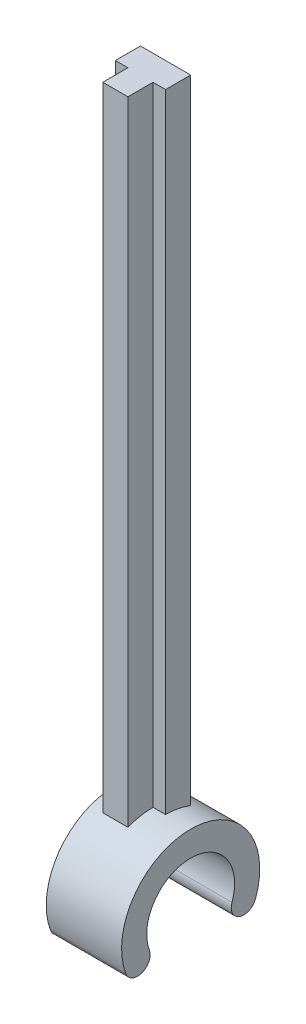
SolidWorks part; units mm, degrees
ref_plane "Front" through (0, 0, 0) normal (0, 0, 1) x (1, 0, 0)
ref_plane "Top" through (0, 0, 0) normal (0, 1, 0) x (1, 0, 0)
ref_plane "Right" through (0, 0, 0) normal (1, 0, 0) x (0, 0, -1)
sketch "Sketch1" plane through (0, 0, 0) normal (1, 0, 0) x (0, 0, -1)
  line L0 (0, 0) -> (-5.5, 0)
  line L1 (0, 0) -> (-5.1683, -1.8811)
  line L2 (0, 50) -> (0, -50) construction
  line L3 (0, 0) -> (5.1683, -1.8811)
  line L4 (-5.1683, -1.8811) -> (-4.2286, -1.5391)
  circle A0 centre (0, 0) radius 3.5
  circle A1 centre (0, 0) radius 5.5
  arc A2 (-5.1683, -1.8811) -> (-3.2889, -1.1971) centre (-4.2286, -1.5391) ccw
  arc A3 (5.1683, -1.8811) -> (3.2889, -1.1971) centre (4.2286, -1.5391) cw
  dimension "D1" = 20
  dimension "D3" = 11
  dimension "D4" = 7
  dimension "D2" = 1
extrude "Boss-Extrude1" add sketch "Sketch1" against normal blind 2 and the other way blind 4 contours L3 A1 L0 A0 | A3 L3 | L0 A1 L1 A0 | L1 A2 region at (0, -0.7903, 4.4817) region at (0, 0.1325, 4.5) region at (0, -1.9379, 4.0835) region at (0, -1.9379, -4.0835)
sketch "Sketch2" plane through (0, 0, 0) normal (1, 0, 0) x (0, 0, -1)
  line L0 (0, 0) -> (0, 5.5)
  line L1 (0, 5.5) -> (0, 3.5)
  line L2 (0, 3.5) -> (-2, 3.5)
  line L3 (0, 55.5) -> (0, 3.5)
  line L4 (-2, 3.5) -> (2, 3.5)
  line L5 (-2, 3.5) -> (-2, 55.5)
  line L6 (-2, 55.5) -> (2, 55.5)
  line L7 (2, 3.5) -> (2, 55.5)
  arc A0 (5.1683, -1.8811) -> (-5.1683, -1.8811) centre (0, 0) ccw construction
  dimension "D1" = 2
  dimension "D2" = 2
  dimension "D3" = 4
  dimension "D4" = 52
extrude "Boss-Extrude2" add sketch "Sketch2" along normal blind 2 and the other way blind 2 contours L4 L7 L6 L3 L0 region at (0, 29.5, -1)
sketch "Sketch3" plane through (0, 0, 0) normal (1, 0, 0) x (0, 0, -1)
  line L5 (0, 55.5) -> (-2, 55.5)
  line L6 (0, 55.5) -> (0, 3.5)
  line L7 (0, 3.5) -> (-2, 3.5)
  line L8 (-2, 55.5) -> (-2, 3.5)
  dimension "D1" = 52
  dimension "D2" = 2
extrude "Boss-Extrude3" add sketch "Sketch3" along normal blind 1 and the other way blind 1
